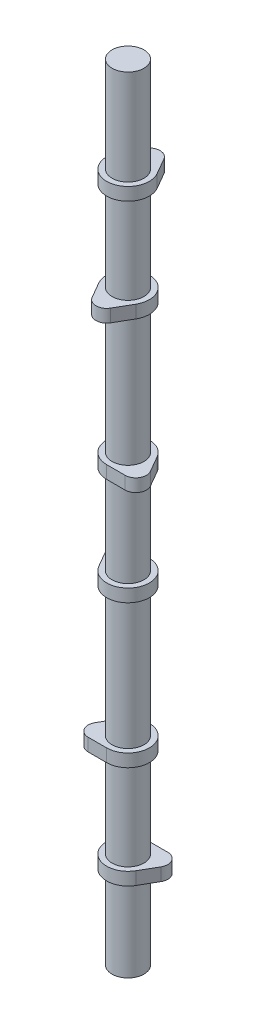
SolidWorks part; units mm, degrees
ref_plane "Front Plane" through (0, 0, 0) normal (0, 0, 1) x (1, 0, 0)
ref_plane "Top Plane" through (0, 0, 0) normal (0, 1, 0) x (1, 0, 0)
ref_plane "Right Plane" through (0, 0, 0) normal (1, 0, 0) x (0, 0, -1)
sketch "Sketch1" plane through (0, 0, 0) normal (0, 1, 0) x (1, 0, 0)
  line L0 (-5.4993, 15.875) -> (-10.9985, 6.35)
  line L1 (5.4993, 15.875) -> (10.9985, 6.35)
  arc A0 (-10.9985, 6.35) -> (10.9985, 6.35) centre (0, 0) ccw
  arc A1 (5.4993, 15.875) -> (-5.4993, 15.875) centre (0, 12.7) ccw
  dimension "D2" = 12.7
  dimension "D3" = 25.4
  dimension "D1" = 12.7
extrude "Boss-Extrude1" add sketch "Sketch1" along normal mid plane 7.62
ref_axis "Axis1" through (0, 13.5001, 0) along (0, -1, 0)
pattern_linear "LPattern1" count 2 spacing 61 along (0, -1, 0) of bodies 101
move or copy body "Body-Move/Copy1" bodies to move or copy 102 copy no rotation origin (0, 0, 0) rotation axis (0, 1, 0) rotation angle 180
pattern_linear "LPattern2" count 3 spacing 146.05 along (0, -1, 0) of bodies 101 104
move or copy body "Body-Move/Copy2" bodies to move or copy 105 107 copy no rotation origin (0, 0, 0) rotation axis (0, -1, 0) rotation angle 120
move or copy body "Body-Move/Copy3" bodies to move or copy 106 108 copy no rotation origin (0, 0, 0) rotation axis (0, 1, 0) rotation angle 120
sketch "Sketch2" plane through (0, 0, 0) normal (0, 1, 0) x (1, 0, 0)
  circle A0 centre (0, 0) radius 9.5
  dimension "D1" = 19
extrude "Boss-Extrude2" add sketch "Sketch2" against normal blind 466.09 and the other way blind 1 from offset 59.53
